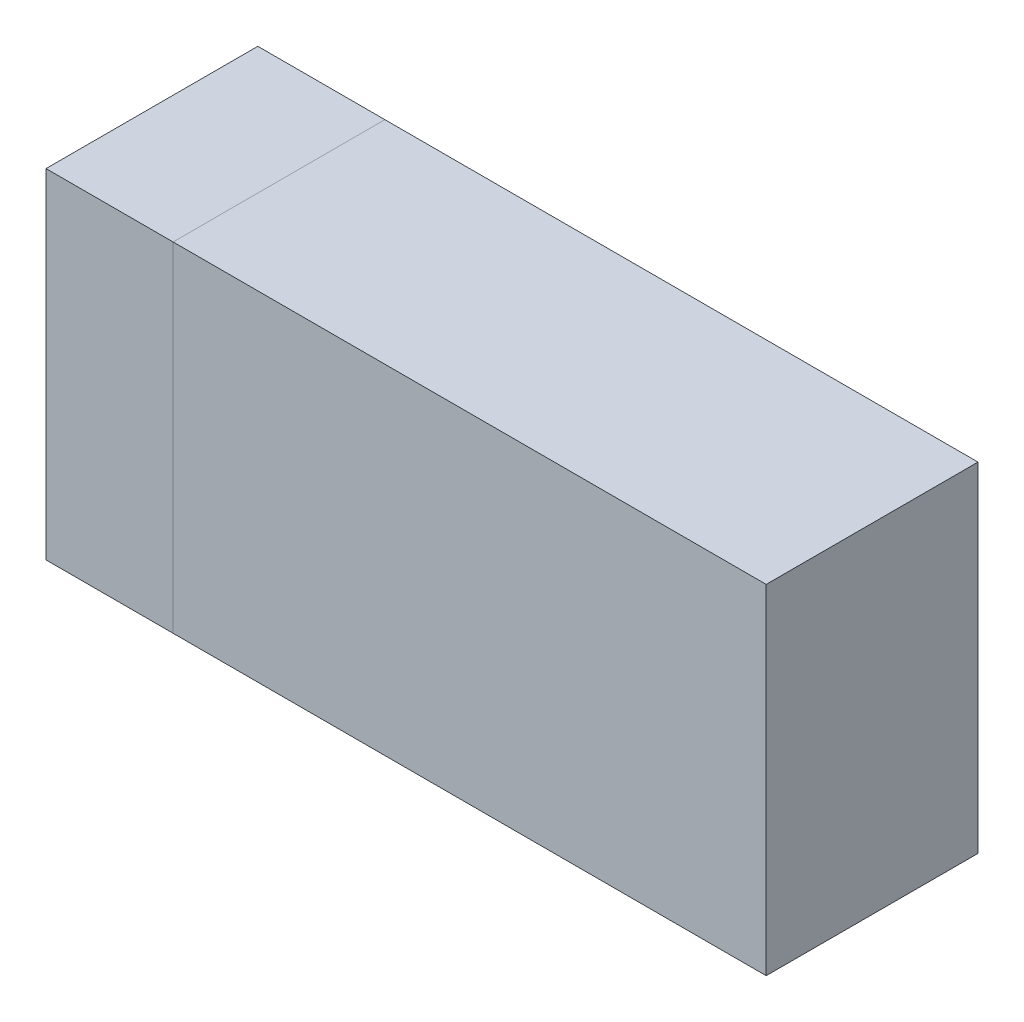
SolidWorks part; units mm, degrees
ref_plane "정면" through (0, 0, 0) normal (0, 0, 1) x (1, 0, 0)
ref_plane "윗면" through (0, 0, 0) normal (0, 1, 0) x (1, 0, 0)
ref_plane "우측면" through (0, 0, 0) normal (1, 0, 0) x (0, 0, -1)
sketch "스케치1" plane through (0, 0, 0) normal (0, 0, 1) x (1, 0, 0)
  line L0 (0, 0) -> (0, 40)
  line L1 (0, 40) -> (-70, 40)
  line L2 (-70, 40) -> (-70, 35)
  line L3 (-70, 35) -> (-5, 35)
  line L4 (-5, 35) -> (-5, 5)
  line L5 (-5, 5) -> (-70, 5)
  line L6 (-70, 5) -> (-70, 0)
  line L7 (-70, 0) -> (0, 0)
  line L9 (0, 6.4259) -> (25, 6.4259)
  line L10 (0, 6.4259) -> (0, 3.7259)
  line L11 (0, 3.7259) -> (25, 3.7259)
  line L12 (25, 6.4259) -> (25, 3.7259)
  line L13 (0, 36.4259) -> (25, 36.4259)
  line L14 (0, 36.4259) -> (0, 33.7259)
  line L15 (0, 33.7259) -> (25, 33.7259)
  line L16 (25, 36.4259) -> (25, 33.7259)
  dimension "D1" = 30
  dimension "D2" = 25
  dimension "D3" = 2.7
  dimension "D4" = 2.7
  dimension "D5" = 5
  dimension "D6" = 5
  dimension "D7" = 5
  dimension "D8" = 70
  dimension "D9" = 40
extrude "보스-돌출1" add sketch "스케치1" along normal blind 25 contours L6 L7 L0 L1 L2 L3 L4 L5 region at (-35, 0.8062, 0)
sketch "스케치2" plane through (0, 0, 0) normal (1, 0, 0) x (0, 0, -1)
  line L0 (-25, 40) -> (0, 40) construction
  line L1 (-25, 0) -> (-22, 0)
  line L2 (-25, 0) -> (-25, 40)
  line L3 (-25, 40) -> (-22, 40)
  line L4 (-22, 0) -> (-22, 40)
  dimension "D1" = 3
extrude "보스-돌출2" add sketch "스케치2" against normal blind 70
sketch "스케치4" plane through (0, 0, 22) normal (0, 0, -1) x (-1, 0, 0)
  line L0 (5, 5) -> (70, 5) construction
  line L1 (60, 5) -> (55, 5)
  line L2 (60, 5) -> (60, 35)
  line L3 (60, 35) -> (55, 35)
  line L4 (55, 5) -> (55, 35)
  line L5 (70, 35) -> (5, 35) construction
  line L6 (5, 35) -> (5, 5) construction
  dimension "D1" = 5
  dimension "D2" = 50
extrude "보스-돌출3" add sketch "스케치4" along normal blind 22 contours L4 L3 L2 L1
sketch "스케치6" plane through (-70, 0, 0) normal (-1, 0, 0) x (0, 0, 1)
  line L0 (25, 0) -> (0, 0) construction
  line L1 (0, 40) -> (3, 40)
  line L2 (0, 40) -> (0, 0)
  line L3 (0, 0) -> (3, 0)
  line L4 (3, 40) -> (3, 0)
  line L6 (25, 0) -> (3, 0)
  line L7 (25, 0) -> (25, 40)
  line L8 (25, 40) -> (3, 40)
  line L9 (3, 0) -> (3, 40)
  line M2 (0, 35) -> (22, 35)
  line M3 (22, 35) -> (22, 5)
  line M4 (22, 5) -> (0, 5)
  line M5 (0, 5) -> (0, 0)
  line M6 (0, 0) -> (25, 0)
  line M7 (25, 0) -> (25, 40)
  line M8 (25, 40) -> (0, 40)
  line M9 (0, 40) -> (0, 35)
  dimension "D1" = 3
sketch "스케치8" plane through (-60, 0, 0) normal (-1, 0, 0) x (0, 0, 1)
  line L1 (11, 45.1187) -> (11, -5.1187) construction
  line L2 (27.432, 20) -> (-5.9023, 20) construction
  line L3 (22, 5) -> (22, 35) construction
  line L4 (0, 35) -> (22, 35) construction
  circle A0 centre (11, 20) radius 4
  point P9 (22, 20)
  point P10 (11, 20)
  point P13 (11, 35)
  dimension "D1" = 8
sketch "스케치11" plane through (-60, 0, 0) normal (-1, 0, 0) x (0, 0, 1)
  line L0 (0, 6.4259) -> (0, 3.7259) construction
  line L1 (0, 5.0759) -> (3, 5.0759)
  line L2 (0, 5.0759) -> (0, 35)
  line L3 (0, 35) -> (3, 35)
  line L4 (3, 5.0759) -> (3, 35)
  line L5 (3, 40) -> (3, 0) construction
  line L6 (0, 35) -> (22, 35) construction
extrude "컷-돌출3" cut sketch "스케치11" against normal blind 7
sketch "스케치12" plane through (0, 0, 22) normal (0, 0, -1) x (-1, 0, 0)
  line L0 (45, 45.3333) -> (45, -8.4936) construction
  line L1 (60, 45.1187) -> (60, -5.1187) construction
  dimension "D1" = 40
sketch "스케치13" plane through (-70, 0, 0) normal (-1, 0, 0) x (0, 0, 1)
  line L0 (0, 36.4259) -> (0, 33.7259) construction
  line L1 (0, 35.0759) -> (3, 35.0759)
  line L2 (0, 35.0759) -> (0, 5.0759)
  line L3 (0, 5.0759) -> (3, 5.0759)
  line L4 (3, 35.0759) -> (3, 5.0759)
  line L6 (0, 40) -> (25, 40)
  line L7 (0, 40) -> (0, 0)
  line L8 (0, 0) -> (25, 0)
  line L9 (25, 40) -> (25, 0)
extrude "보스-돌출5" add sketch "스케치13" against normal up to vertex (25 mm away) separate body contours L1 L4 L3 L2 up to point (-45, 45.3333, 22)
extrude "보스-돌출6" add sketch "스케치6" along normal blind 15 contours L4 M4 M5 M6 | L4 L2 M2 M4 | L4 M8 M9 M2 | L4 M2 M4 M3 | L4 M8 M2 M3 M4 M6 M7 | L9 L6 L7 L8 region at (-70, 37.5, 1.5) region at (-70, 39.5435, 14) region at (-70, 20, 1.5) region at (-70, 20, 12.5) region at (-70, 2.5, 1.5)
sketch "스케치14" plane through (-70, 0, 0) normal (1, 0, 0) x (0, 0, -1)
  line L0 (-22, 0) -> (-22, 40) construction
  line L1 (-22, 37) -> (-3, 37)
  line L2 (-22, 37) -> (-22, 3)
  line L3 (-22, 3) -> (-3, 3)
  line L4 (-3, 37) -> (-3, 3)
  line L5 (-3, 35.0759) -> (-3, 5.0759) construction
  line L6 (-25, 40) -> (0, 40) construction
  line L7 (0, 0) -> (-25, 0) construction
  circle A0 centre (-11, 20) radius 4
  dimension "D1" = 3
  dimension "D2" = 3
extrude "컷-돌출4" cut sketch "스케치14" against normal blind 7
extrude "컷-돌출5" cut sketch "스케치14<2>" against normal blind 9 contours A0 region at (-70, 20, 11)
sketch "스케치14<2>" plane through (-70, 0, 0) normal (1, 0, 0) x (0, 0, -1) same geometry as "스케치14"
